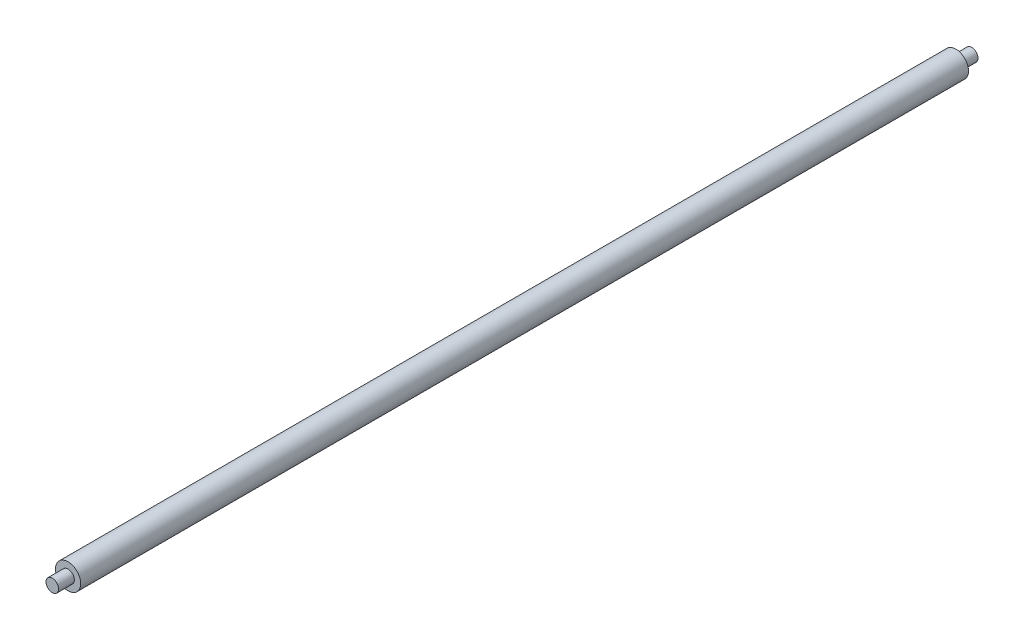
SolidWorks part; units mm, degrees
ref_plane "Front Plane" through (0, 0, 0) normal (0, 0, 1) x (1, 0, 0)
ref_plane "Top Plane" through (0, 0, 0) normal (0, 1, 0) x (1, 0, 0)
ref_plane "Right Plane" through (0, 0, 0) normal (1, 0, 0) x (0, 0, -1)
sketch "Sketch1" plane through (0, 0, 0) normal (0, 0, 1) x (1, 0, 0)
  circle A0 centre (0, 0) radius 6
  dimension "D1" = 12
extrude "Boss-Extrude1" add sketch "Sketch1" along normal mid plane 422.5
sketch "Sketch2" plane through (0, 0, 211.25) normal (0, 0, 1) x (1, 0, 0)
  circle A1 centre (0, 0) radius 3
  dimension "D2" = 6
sketch "Sketch3" plane through (0, 0, -211.25) normal (0, 0, -1) x (-1, 0, 0)
  circle A1 centre (0, 0) radius 3
  dimension "D1" = 6
extrude "Boss-Extrude4" add sketch "Sketch2" along normal blind 7.5
extrude "Boss-Extrude5" add sketch "Sketch3" along normal blind 7.5
